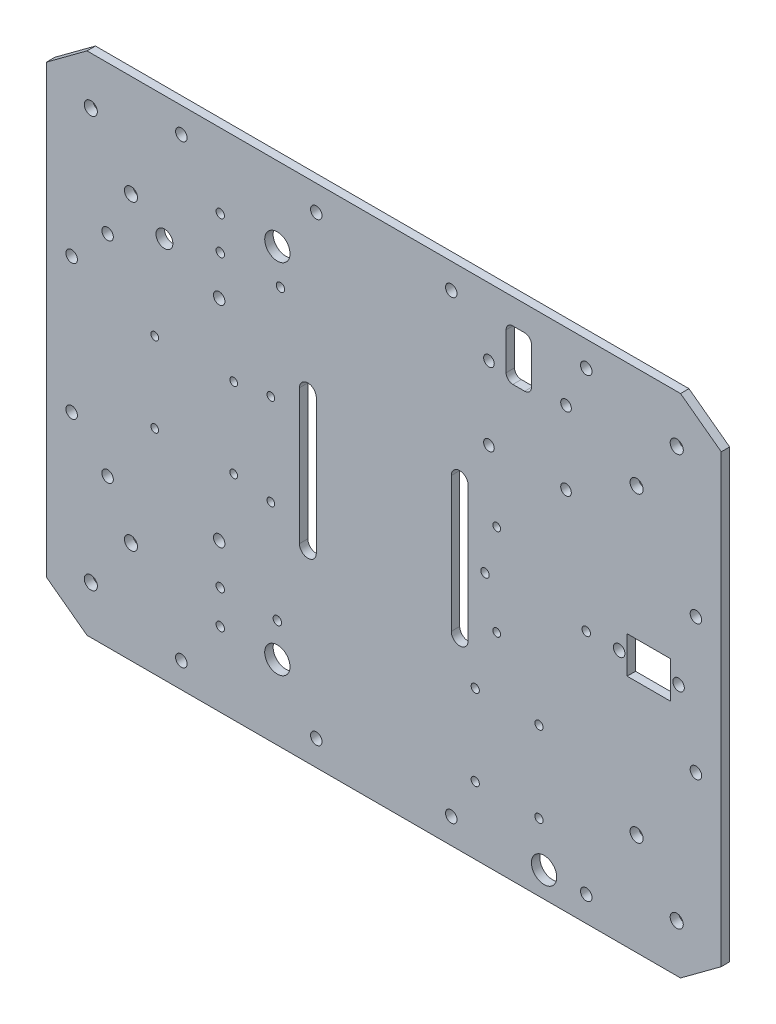
SolidWorks part; units mm, degrees
material "Thornel Mat VMA"
ref_plane "Front Plane" through (0, 0, 0) normal (0, 0, 1) x (1, 0, 0)
ref_plane "Top Plane" through (0, 0, 0) normal (0, 1, 0) x (1, 0, 0)
ref_plane "Right Plane" through (0, 0, 0) normal (1, 0, 0) x (0, 0, -1)
sketch "Sketch1" plane through (0, 0, 0) normal (0, 0, 1) x (1, 0, 0)
  line L0 (-127, 0) -> (127, 0) construction
  line L1 (0, -95.25) -> (0, 95.25) construction
  line L2 (-107.95, 0) -> (-107.95, 41.011) construction
  line L3 (-107.95, 41.011) -> (-95.25, 41.011) construction
  line L4 (-95.25, 41.011) -> (-79.9365, 52.3423) construction
  line L5 (-79.9365, 52.3423) -> (-79.9365, 76.2) construction
  line L6 (-79.9365, 76.2) -> (0, 76.2) construction
  line L7 (-95.25, 41.011) -> (-127, 83.9186) construction
  line L8 (-79.9365, 52.3423) -> (-111.6865, 95.25) construction
  line L9 (-111.6865, -95.25) -> (-127, -83.9186)
  line L10 (111.6865, -95.25) -> (127, -83.9186)
  line L11 (111.6865, 95.25) -> (127, 83.9186)
  line L12 (-87.5933, 46.6767) -> (-95.1475, 56.8856) construction
  line L13 (-95.1475, 56.8856) -> (-110.256, 77.3036) construction
  line L24 (127, -83.9186) -> (127, 83.9186)
  line L26 (111.6865, 95.25) -> (-111.6865, 95.25)
  line L27 (-111.6865, 95.25) -> (-127, 83.9186)
  line L28 (-127, 83.9186) -> (-127, -83.9186)
  line L30 (-111.6865, -95.25) -> (111.6865, -95.25)
  circle A0 centre (-95.1475, 56.8856) radius 2.4638
  circle A1 centre (-110.256, 77.3036) radius 2.4638
  circle A2 centre (110.256, 77.3036) radius 2.4638
  circle A3 centre (95.1475, 56.8856) radius 2.4638
  circle A4 centre (-110.256, -77.3036) radius 2.4638
  circle A5 centre (-95.1475, -56.8856) radius 2.4638
  circle A6 centre (110.256, -77.3036) radius 2.4638
  circle A7 centre (95.1475, -56.8856) radius 2.4638
  point P12 (0, 0)
  dimension "D1" = 190.5
  dimension "D2" = 254
  dimension "D3" = 19.05
  dimension "D4" = 19.05
  dimension "D5" = 12.7
  dimension "D6" = 19.05
  dimension "D7" = 143.5
  dimension "D8" = 12.7
  dimension "D9" = 25.4
extrude "Boss-Extrude1" add sketch "Sketch1" along normal blind 3.175
sketch "Sketch2" plane through (0, 0, 3.175) normal (0, 0, 1) x (1, 0, 0)
  line L0 (-127, 0) -> (127, 0) construction
  line L1 (-127, 83.9186) -> (-127, -83.9186) construction
  line L2 (127, -83.9186) -> (127, 83.9186) construction
  line L3 (57.15, 65.0875) -> (57.15, -65.0875) construction
  line L4 (38.1, 65.0875) -> (76.2, 65.0875)
  line L5 (38.1, 65.0875) -> (38.1, -65.0875)
  line L6 (38.1, -65.0875) -> (76.2, -65.0875)
  line L7 (76.2, 65.0875) -> (76.2, -65.0875)
  line L8 (38.1, 65.0875) -> (76.2, -65.0875) construction
  line L9 (38.1, -65.0875) -> (76.2, 65.0875) construction
  line L10 (57.15, 58.7375) -> (47.625, 58.7375) construction
  line L11 (47.625, 58.7375) -> (38.1, 58.7375) construction
  line L12 (99.7726, 0) -> (99.7726, 35.1373) construction
  line L13 (91.5811, -6.9215) -> (107.9641, -6.9215)
  line L14 (91.5811, -6.9215) -> (91.5811, 6.9215)
  line L15 (91.5811, 6.9215) -> (107.9641, 6.9215)
  line L16 (107.9641, -6.9215) -> (107.9641, 6.9215)
  line L17 (91.5811, -6.9215) -> (107.9641, 6.9215) construction
  line L18 (91.5811, 6.9215) -> (107.9641, -6.9215) construction
  circle A0 centre (42.8625, 58.7375) radius 2.159
  circle A1 centre (42.8625, -58.7375) radius 2.159
  circle A2 centre (71.4375, -58.7375) radius 2.159
  circle A3 centre (71.4375, 58.7375) radius 2.159
  circle A4 centre (110.9486, 0) radius 2.159
  circle A5 centre (88.5966, 0) radius 2.159
  point P6 (57.15, 0)
  point P17 (42.8625, 58.7375)
  point P25 (99.7726, 0)
  dimension "D6" = 13.843
  dimension "D8" = 11.176
  dimension "D1" = 38.1
  dimension "D2" = 130.175
  dimension "D3" = 6.35
  dimension "D4" = 9.525
  dimension "D5" = 69.85
  dimension "D7" = 16.383
extrude "Cut-Extrude1" cut sketch "Sketch2" against normal through all contours L13 L16 L15 L14 | A5 | A4 region at (99.7726, 0, 3.175) region at (110.9486, 0, 3.175) region at (88.5966, 0, 3.175)
sketch "Sketch3" plane through (0, 0, 3.175) normal (0, 0, 1) x (1, 0, 0)
  line L0 (0, 95.25) -> (0, -95.25) construction
  line L1 (111.6865, 95.25) -> (-111.6865, 95.25) construction
  line L2 (-111.6865, -95.25) -> (111.6865, -95.25) construction
  line L3 (127, 0) -> (-127, 0) construction
  line L4 (127, -83.9186) -> (127, 83.9186) construction
  line L5 (-127, 83.9186) -> (-127, -83.9186) construction
sketch "Sketch5" plane through (0, 0, 0) normal (0, 0, -1) x (-1, 0, 0)
  line L0 (-127, 0) -> (127, 0) construction
  line L1 (107.95, 43.5) -> (57.9501, 43.5) construction
  line L2 (107.95, 43.5) -> (107.95, -43.5) construction
  line L3 (107.95, -43.5) -> (57.9501, -43.5) construction
  line L4 (57.9501, 43.5) -> (57.9501, -43.5) construction
  line L5 (89.4966, 18.0341) -> (89.4966, -18.0339)
  line L6 (67.8946, 95.25) -> (67.8946, -95.25) construction
  line L7 (111.6865, -95.25) -> (-111.6865, -95.25) construction
  line L8 (0, 64.0679) -> (0, -49.8393) construction
  line L9 (-42.5, 17.2) -> (42.5, 17.2) construction
  line L10 (-42.5, 17.2) -> (-42.5, -17.2) construction
  line L11 (-42.5, -17.2) -> (42.5, -17.2) construction
  line L12 (42.5, 17.2) -> (42.5, -17.2) construction
  line L13 (-42.5, 17.2) -> (42.5, -17.2) construction
  line L14 (-42.5, -17.2) -> (42.5, 17.2) construction
  line L15 (46.8402, 60.96) -> (31.75, 60.96) construction
  line L16 (61.5446, -67.31) -> (-87.4336, -67.31) construction
  line L17 (-127, -83.9186) -> (-127, 83.9186) construction
  line L18 (40.0554, 67.31) -> (18.5661, 67.31) construction
  line L19 (-28.575, 25.4) -> (-28.575, -25.4) construction
  line L20 (127, 83.9186) -> (127, -83.9186) construction
  line L21 (-127, -83.9186) -> (-127, 83.9186) construction
  line L22 (-50.8, 76.2) -> (82.55, 76.2) construction
  line L23 (82.55, 76.2) -> (82.55, 48.58) construction
  line L25 (82.55, -77.0458) -> (82.55, 48.58) construction
  line L26 (127, 0) -> (-127, 0) construction
  line L27 (82.95, 0) -> (82.9501, -8419.0368) construction
  line L28 (-25.4, 25.4) -> (-25.4, -25.4)
  line L29 (-31.75, 25.4) -> (-31.75, -25.4)
  line L30 (28.575, 25.4) -> (28.575, -25.4) construction
  line L31 (25.4, 25.4) -> (25.4, -25.4)
  line L32 (31.75, 25.4) -> (31.75, -25.4)
  line L33 (71.3384, 0) -> (71.3384, 12.3782) construction
  line L34 (53.4794, 18.0341) -> (89.4966, 18.0341)
  line L35 (53.4794, 18.0341) -> (53.4794, -18.0339)
  line L36 (53.4794, -18.0339) -> (89.4966, -18.0339)
  line L37 (-46.0375, 66.675) -> (-55.5625, 66.675)
  line L38 (-46.0375, 66.675) -> (-46.0375, 85.725)
  line L39 (-46.0375, 85.725) -> (-55.5625, 85.725)
  line L40 (-50.8, 76.2) -> (-50.8, 95.25) construction
  line L41 (-55.5625, 66.675) -> (-55.5625, 85.725)
  line L42 (-46.0375, 66.675) -> (-55.5625, 85.725) construction
  line L43 (-46.0375, 85.725) -> (-55.5625, 66.675) construction
  line L47 (-127, -83.9186) -> (-127, 83.9186) construction
  line L48 (-111.6865, 95.25) -> (111.6865, 95.25) construction
  circle A0 centre (61.5446, -54.61) radius 1.5875
  circle A1 centre (61.5446, -67.31) radius 1.5875
  circle A2 centre (82.55, 48.58) radius 3.175
  circle A3 centre (-60.325, -85.725) radius 4.7625
  circle A4 centre (61.5446, 54.61) radius 1.5875
  circle A7 centre (40.0554, -67.31) radius 4.7625
  circle A8 centre (61.5446, 67.31) radius 1.5875
  circle A10 centre (40.0554, 67.31) radius 4.7625
  circle A12 centre (61.9506, 39.4995) radius 2.159
  circle A13 centre (103.9495, 39.4995) radius 2.159
  circle A14 centre (61.9506, -39.4995) radius 2.159
  circle A15 centre (103.9495, -39.4995) radius 2.159
  circle A17 centre (38.8861, 54.61) radius 1.5875
  circle A19 centre (40.0554, -54.61) radius 1.5875
  arc A20 (-25.4, 25.4) -> (-31.75, 25.4) centre (-28.575, 25.4) ccw
  arc A21 (-31.75, -25.4) -> (-25.4, -25.4) centre (-28.575, -25.4) ccw
  arc A22 (25.4, 25.4) -> (31.75, 25.4) centre (28.575, 25.4) cw
  arc A23 (31.75, -25.4) -> (25.4, -25.4) centre (28.575, -25.4) cw
  circle A24 centre (56.4794, 15.0341) radius 1.4478
  circle A25 centre (56.4794, -15.0341) radius 1.4478
  circle A26 centre (86.1974, -15.0341) radius 1.4478
  circle A27 centre (86.1974, 15.0341) radius 1.4478
  circle A28 centre (-42.5, 17.2) radius 1.4542
  circle A29 centre (-42.5, -17.2) radius 1.4541
  circle A30 centre (42.5, -17.2) radius 1.4541
  circle A31 centre (42.5, 17.2) radius 1.4542
  point P0 (82.95, 0)
  point P9 (0, 0)
  point P77 (-28.575, 0)
  point P84 (28.575, 0)
  point P89 (71.3384, 0)
  dimension "D10" = 6.35
  dimension "D15" = 2.9997
  dimension "D17" = 66.675
  dimension "D18" = 41.9989
  dimension "D22" = 76.2
  dimension "D25" = 4.0005
  dimension "D45" = 2.8956
  dimension "D9" = 9.525
  dimension "D13" = 14.859
  dimension "D14" = 3
  dimension "D20" = 9.525
  dimension "D8" = 9.525
  dimension "D19" = 19.05
  dimension "D16" = 9.525
  dimension "D1" = 87.0001
  dimension "D2" = 49.9999
  dimension "D4" = 34.4
  dimension "D5" = 85
  dimension "D6" = 6.35
  dimension "D7" = 19.05
  dimension "D11" = 5.08
  dimension "D12" = 25.4
  dimension "D24" = 19.05
  dimension "D26" = 4.0005
  dimension "D38" = 50.8
  dimension "D39" = 6.35
  dimension "D40" = 28.575
  dimension "D41" = 36.0172
  dimension "D42" = 36.068
  dimension "D44" = 3
extrude "Cut-Extrude2" cut sketch "Sketch5" against normal through all contours A2 | A14 | A15 | A13 | A12 | L29 A21 L28 A20 | A23 L4 A22 L31 | A23 L32 A22 L4 | A27 | A24 | A25 | A26
sketch "Sketch6" plane through (0, 0, 0) normal (0, 0, -1) x (-1, 0, 0)
  line L0 (0, 0) -> (-135.1326, 0) construction
  line L1 (0, 0) -> (0, -95.25) construction
  line L2 (111.6865, -95.25) -> (-111.6865, -95.25) construction
  line L3 (-76.2, -95.25) -> (-76.2, -85.725) construction
  line L4 (117.475, 0) -> (117.475, -25.4) construction
  line L5 (127, 0) -> (-127, 0) construction
  line L6 (127, 83.9186) -> (127, -83.9186) construction
  circle A0 centre (-76.2, -85.725) radius 2.159
  circle A1 centre (-25.4, -85.725) radius 2.159
  circle A2 centre (25.4, -85.725) radius 2.159
  circle A3 centre (76.2, -85.725) radius 2.159
  circle A4 centre (76.2, 85.725) radius 2.159
  circle A5 centre (25.4, 85.725) radius 2.159
  circle A6 centre (-25.4, 85.725) radius 2.159
  circle A7 centre (-76.2, 85.725) radius 2.159
  circle A8 centre (117.475, -25.4) radius 2.159
  circle A9 centre (117.475, 25.4) radius 2.159
  circle A10 centre (-117.475, 25.4) radius 2.159
  circle A11 centre (-117.475, -25.4) radius 2.159
  dimension "D2" = 9.525
  dimension "D3" = 76.2
  dimension "D5" = 9.525
  dimension "D6" = 25.4
  dimension "D4" = 4
extrude "Cut-Extrude3" cut sketch "Sketch6" against normal through all
extrude "Cut-Extrude4" cut sketch "Sketch5<3>" against normal through all contours A28 | A29 | A31 | A30
sketch "Sketch5<3>" plane through (0, 0, 0) normal (0, 0, -1) x (-1, 0, 0) same geometry as "Sketch5"
extrude "Cut-Extrude5" cut sketch "Sketch5<4>" against normal through all contours A3 | A10 | A8 | A4 | A0 | A1 | A7 region at (60.325, -85.725, 0)
sketch "Sketch5<4>" plane through (0, 0, 0) normal (0, 0, -1) x (-1, 0, 0) same geometry as "Sketch5"
extrude "Cut-Extrude6" cut sketch "Sketch5<5>" against normal blind 2.54 contours A17
sketch "Sketch5<5>" plane through (0, 0, 0) normal (0, 0, -1) x (-1, 0, 0) same geometry as "Sketch5"
extrude "Cut-Extrude7" cut sketch "Sketch5<6>" against normal through all contours A17
sketch "Sketch5<6>" plane through (0, 0, 0) normal (0, 0, -1) x (-1, 0, 0) same geometry as "Sketch5"
extrude "Cut-Extrude8" cut sketch "Sketch5<7>" against normal blind 2.54 and the other way blind 7.62 contours L41 L37 L38 L39 | A19
sketch "Sketch5<7>" plane through (0, 0, 0) normal (0, 0, -1) x (-1, 0, 0) same geometry as "Sketch5"
extrude "Cut-Extrude9" cut sketch "Sketch5<9>" against normal through all contours A19
sketch "Sketch5<9>" plane through (0, 0, 0) normal (0, 0, -1) x (-1, 0, 0) same geometry as "Sketch5"
extrude "Cut-Extrude17" cut sketch "Sketch5<15>" against normal through all both and the other way through all contours L39 L41 L37 L38
sketch "Sketch5<15>" plane through (0, 0, 0) normal (0, 0, -1) x (-1, 0, 0) same geometry as "Sketch5"
fillet "Fillet1" radius 2.54 1 edges at (55.5625, 85.725, 1.5875) type face fillet first side face at (55.5625, 76.2, 1.5875) second side face at (50.8, 85.725, 1.5875)
fillet "Fillet2" radius 2.54 1 edges at (46.0375, 85.725, 1.5875) type face fillet first side face at (49.53, 85.725, 1.5875) second side face at (46.0375, 76.2, 1.5875)
fillet "Fillet3" radius 2.54 1 edges at (46.0375, 66.675, 1.5875) type face fillet first side face at (50.8, 66.675, 1.5875) second side face at (46.0375, 74.93, 1.5875)
fillet "Fillet4" radius 2.54 1 edges at (55.5625, 66.675, 1.5875) type face fillet first side face at (52.07, 66.675, 1.5875) second side face at (55.5625, 74.93, 1.5875)
sketch "Sketch9" plane through (0, 0, 3.175) normal (0, 0, 1) x (1, 0, 0)
  line L0 (127, -83.9186) -> (127, 83.9186) construction
  line L1 (34.42, -39.45) -> (58.42, -39.45) construction
  line L2 (34.42, -39.45) -> (34.42, -69.85) construction
  line L3 (34.42, -69.85) -> (58.42, -69.85) construction
  line L4 (58.42, -39.45) -> (58.42, -69.85) construction
  line L5 (-111.6865, -95.25) -> (111.6865, -95.25) construction
  line L6 (127, -83.9186) -> (127, 83.9186) construction
  line L7 (68.58, 69.85) -> (39.58, 69.85) construction
  line L8 (68.58, 69.85) -> (68.58, 42.35) construction
  line L9 (68.58, 42.35) -> (39.58, 42.35) construction
  line L10 (39.58, 69.85) -> (39.58, 42.35) construction
  line L11 (111.6865, 95.25) -> (-111.6865, 95.25) construction
  line L12 (127, 0) -> (0, 0) construction
  circle A0 centre (34.42, -39.45) radius 1.55
  circle A1 centre (58.42, -39.45) radius 1.55
  circle A2 centre (58.42, -69.85) radius 1.55
  circle A3 centre (34.42, -69.85) radius 1.55
  circle A4 centre (68.58, 69.85) radius 2
  circle A5 centre (39.58, 69.85) radius 2
  circle A6 centre (39.58, 42.35) radius 2
  circle A7 centre (68.58, 42.35) radius 2
  circle A8 centre (76.2, 0) radius 1.5875
  circle A9 centre (38.1, 0) radius 1.5875
  dimension "D1" = 3.1
  dimension "D6" = 4
  dimension "D11" = 3.175
  dimension "D12" = 3.175
  dimension "D13" = 38.1
  dimension "D2" = 30.4
  dimension "D3" = 24
  dimension "D4" = 68.58
  dimension "D5" = 25.4
  dimension "D7" = 29
  dimension "D8" = 27.5
  dimension "D9" = 58.42
  dimension "D10" = 25.4
  dimension "D14" = 50.8
extrude "Cut-Extrude18" cut sketch "Sketch9" against normal through all
